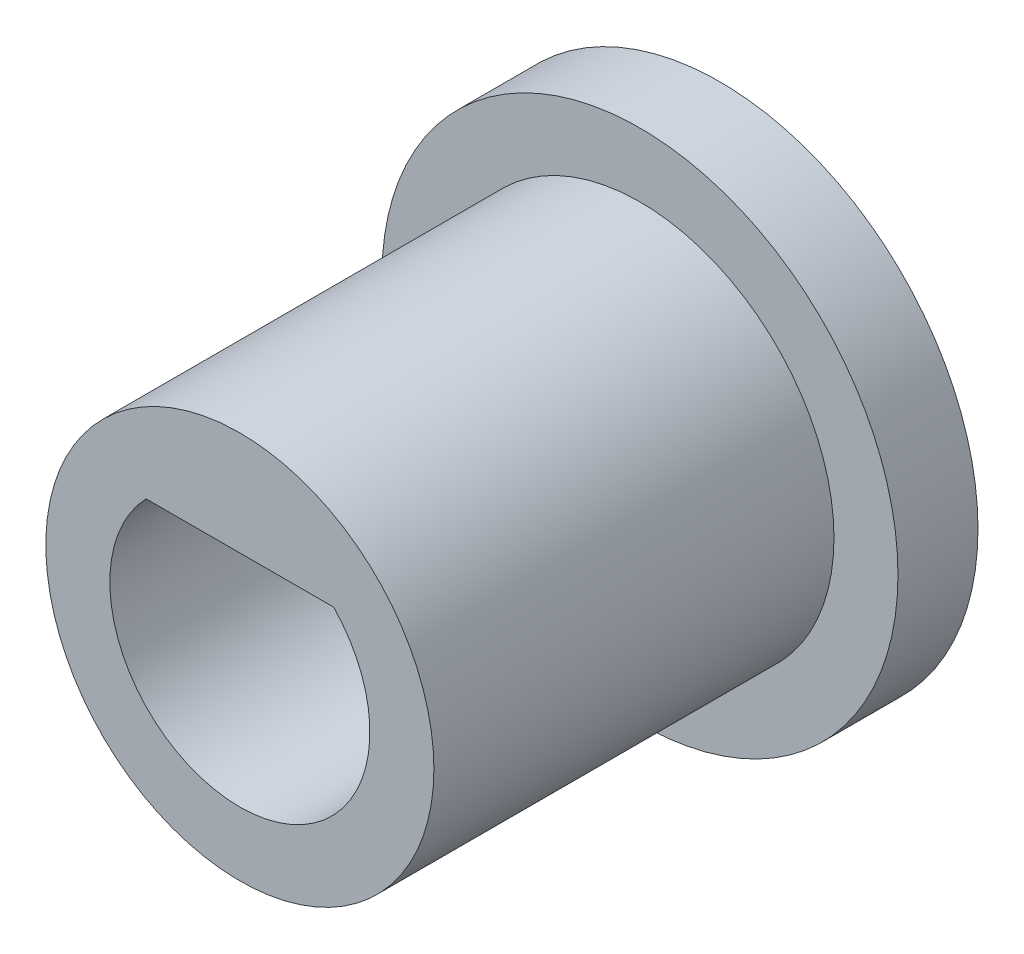
SolidWorks part; units mm, degrees
ref_plane "Front" through (0, 0, 0) normal (0, 0, 1) x (1, 0, 0)
ref_plane "Top" through (0, 0, 0) normal (0, 1, 0) x (1, 0, 0)
ref_plane "Right" through (0, 0, 0) normal (1, 0, 0) x (0, 0, -1)
sketch "Sketch1" plane through (0, 0, 0) normal (0, 0, 1) x (1, 0, 0)
  line L0 (-1.1726, 1.125) -> (1.1726, 1.125)
  circle A0 centre (0, 0) radius 2.425
  circle A1 centre (0, 0) radius 1.625
  circle A2 centre (0, 0) radius 3.225
  point P6 (0, -1.625)
  dimension "D1" = 0.8
  dimension "D2" = 3.25
  dimension "D4" = 1.6
  dimension "D3" = 2.75
extrude "Boss-Extrude1" add sketch "Sketch1" along normal blind 5 contours L0 A1 | A0 A1 region at (0, 1.3279, 0) region at (-2.3564, 0, 0)
extrude "Boss-Extrude2" add sketch "Sketch1<4>" against normal blind 1 contours A2 A0 | A0 A1 | L0 A1 region at (0, 1.3279, 0) region at (-2.3564, 0, 0) region at (-3.1338, 0, 0)
sketch "Sketch1<4>" plane through (0, 0, 0) normal (0, 0, 1) x (1, 0, 0) same geometry as "Sketch1"
equation "\"D3@Sketch1\"=\"axle_cut\"+\"axle_room\""
equation "\"axle_dia\"= 3"
equation "\"axle_cut\"= 2.5"
equation "\"axle_room\"= 0.25"
equation "\"print_thickness\"= 0.4"
equation "\"D4@Sketch1\"=\"print_thickness\"*4"
equation "\"D1@Sketch1\"=\"print_thickness\"*2"
equation "\"D2@Sketch1\"=\"axle_dia\"+\"axle_room\""
